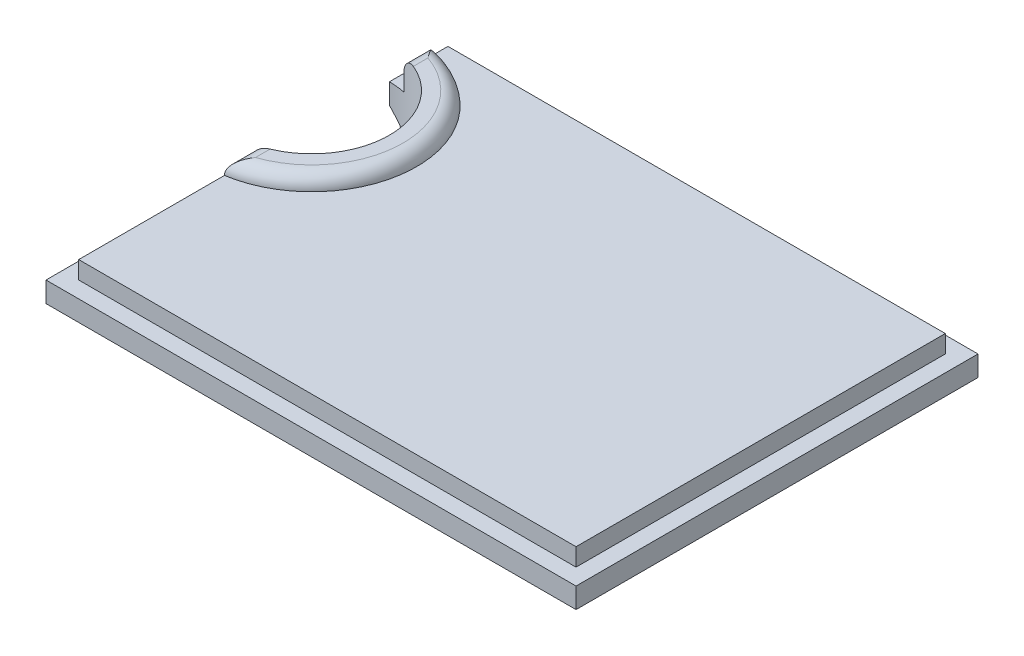
SolidWorks part; units mm, degrees
ref_plane "Front Plane" through (0, 0, 0) normal (0, 0, 1) x (1, 0, 0)
ref_plane "Top Plane" through (0, 0, 0) normal (0, 1, 0) x (1, 0, 0)
ref_plane "Right Plane" through (0, 0, 0) normal (1, 0, 0) x (0, 0, -1)
sketch "Sketch1" plane through (0, 0, 0) normal (0, 1, 0) x (1, 0, 0)
  line L0 (-19.45, 14.75) -> (-19.45, -14.75)
  line L1 (-19.45, -14.75) -> (19.45, -14.75)
  line L2 (19.45, -14.75) -> (19.45, 14.75)
  line L3 (19.45, 14.75) -> (-19.45, 14.75)
  line L4 (18.25, 13.55) -> (-18.25, 13.55)
  line L5 (-18.25, 13.55) -> (-18.25, -13.55)
  line L6 (-18.25, -13.55) -> (18.25, -13.55)
  line L7 (18.25, -13.55) -> (18.25, 13.55)
  line L8 (-18.25, 13.55) -> (0, 0) construction
  line L9 (0, 0) -> (18.25, -13.55) construction
  line L10 (0, 0) -> (18.25, 13.55) construction
  line L11 (0, 0) -> (-18.25, -13.55) construction
  arc A0 (-19.45, 10.45) -> (-19.45, -0.95) centre (-19.45, 4.75) cw
  arc A1 (-19.45, 12.45) -> (-19.45, -2.95) centre (-19.45, 4.75) cw
  dimension "D4" = 5.7
  dimension "D6" = 2
  dimension "D1" = 29.5
  dimension "D2" = 38.9
  dimension "D5" = 10
  dimension "D3" = 1.2
extrude "Boss-Extrude1" add sketch "Sketch1" along normal blind 1 contours L5 A1 L6 L7 L4 | A1 L5 A0 | L0 A1 L5 L4 L7 L6 L1 L2 L3 | A1 L5 A0 L0 | A1 L0 A0 L5 region at (0, 0, -14.2618) region at (-18.8483, 0, -11.413) region at (-11.9154, 0, -4.75) region at (1.2687, 0, 0.3882) region at (-18.8483, 0, 1.913)
extrude "Boss-Extrude2" add sketch "Sketch1<5>" along normal blind 1.6 from surface contours L5 A1 L6 L7 L4 | A1 L5 A0 | A1 L0 A0 L5 | L0 A1 L5 L4 L7 L6 L1 L2 L3 | A1 L5 A0 L0 region at (0, 0, -14.2618) region at (-18.8483, 0, -11.413) region at (-11.9154, 0, -4.75) region at (1.2687, 0, 0.3882) region at (-18.8483, 0, 1.913) starting at face at (-5.5333, 1, -1.5833)
sketch "Sketch1<5>" plane through (0, 0, 0) normal (0, 1, 0) x (1, 0, 0) same geometry as "Sketch1"
extrude "Boss-Extrude3" add sketch "Sketch1<6>" along normal blind 1.3 from surface contours L5 A1 L6 L7 L4 | A1 L5 A0 region at (-11.9154, 0, -4.75) region at (1.2687, 0, 0.3882) starting at face at (-5.5333, 2.6, -1.5833)
sketch "Sketch1<6>" plane through (0, 0, 0) normal (0, 1, 0) x (1, 0, 0) same geometry as "Sketch1"
extrude "Boss-Extrude4" add sketch "Sketch1<8>" along normal blind 1 from surface contours A1 L5 A0 region at (-11.9154, 0, -4.75) starting at face at (-5.3333, 3.9, -1.5833)
sketch "Sketch1<8>" plane through (0, 0, 0) normal (0, 1, 0) x (1, 0, 0) same geometry as "Sketch1"
fillet "Fillet1" radius 1 3 edges at (-11.75, 4.9, -4.75) (-18.25, 4.9, 1.8391) (-18.25, 4.9, -11.3391)
chamfer "Chamfer1" distance 1.1 angle 45 5 edges at (-19.45, 0, -12.6) (0, 0, -14.75) (19.45, 0, 0) (0, 0, 14.75) (-19.45, 0, 7.85)
